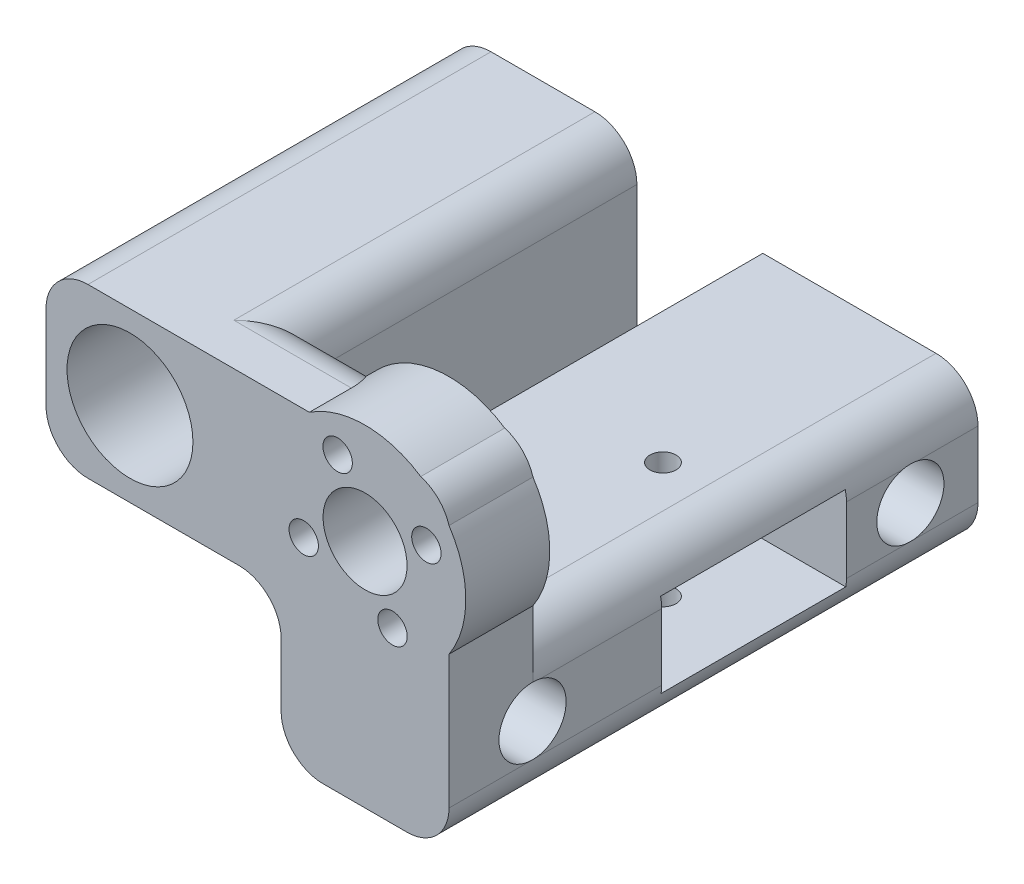
SolidWorks part; units mm, degrees
ref_plane "前视基准面" through (0, 0, 0) normal (0, 0, 1) x (1, 0, 0)
ref_plane "上视基准面" through (0, 0, 0) normal (0, 1, 0) x (1, 0, 0)
ref_plane "右视基准面" through (0, 0, 0) normal (1, 0, 0) x (0, 0, -1)
sketch "草图1" plane through (0, 0, 0) normal (0, 1, 0) x (1, 0, 0)
  line L1 (-10.5078, 7.8964) -> (37.4922, 7.8964)
  line L2 (-10.5078, 7.8964) -> (-10.5078, -40.1036)
  line L3 (-10.5078, -40.1036) -> (37.4922, -40.1036)
  line L4 (37.4922, 7.8964) -> (37.4922, -40.1036)
  line L5 (-10.5078, 7.8964) -> (37.4922, -40.1036) construction
  line L6 (-10.5078, -40.1036) -> (37.4922, 7.8964) construction
  point P4 (13.4922, -16.1036)
  dimension "D1" = 48
  dimension "D2" = 48
extrude "凸台-拉伸1" add sketch "草图1" along normal blind 40
sketch "草图2" plane through (0, 0, 40.1036) normal (0, 0, 1) x (1, 0, 0)
  line L0 (-10.5078, 40) -> (37.4922, 40) construction
  line L1 (-10.5078, 40) -> (-10.5078, 0) construction
  circle A0 centre (-0.5078, 30) radius 7.5
  circle A1 centre (27.4922, 30) radius 5
  circle A2 centre (24.2267, 37.3032) radius 1.75
  circle A3 centre (34.7954, 33.2656) radius 1.75
  circle A4 centre (20.1891, 26.7344) radius 1.75
  circle A5 centre (30.7578, 22.6968) radius 1.75
  dimension "D1" = 15
  dimension "D2" = 10
  dimension "D4" = 10
  dimension "D5" = 10
  dimension "D3" = 28
extrude "切除-拉伸1" cut sketch "草图2" against normal through all
sketch "草图3" plane through (0, 0, 40.1036) normal (0, 0, 1) x (1, 0, 0)
  circle A0 centre (27.4922, 30) radius 12
  circle A1 centre (27.4922, 30) radius 5.5
  circle A2 centre (24.2267, 37.3032) radius 1.75
  circle A3 centre (20.1891, 26.7344) radius 1.75
  circle A4 centre (30.7578, 22.6968) radius 1.75
  circle A5 centre (34.7954, 33.2656) radius 1.75
  dimension "D1" = 24
  dimension "D2" = 11
extrude "凸台-拉伸3" add sketch "草图3" against normal blind 10
sketch "草图4" plane through (0, 0, -7.8964) normal (0, 0, -1) x (-1, 0, 0)
  line L1 (-37.4922, 40) -> (-11.8688, 40)
  line L2 (-37.4922, 40) -> (-37.4922, 20.3994)
  line L3 (-37.4922, 20.3994) -> (-11.8688, 20.3994)
  line L4 (-11.8688, 40) -> (-11.8688, 20.3994)
  line L5 (-37.4922, 40) -> (-11.8688, 20.3994) construction
  line L6 (-37.4922, 20.3994) -> (-11.8688, 40) construction
  point P4 (-24.6805, 30.1997)
extrude "切除-拉伸2" cut sketch "草图4" against normal blind 38
fillet "圆角1" radius 5 1 edges at (37.4922, 40, 35.1036)
sketch "草图5" plane through (37.4922, 0, 0) normal (1, 0, 0) x (0, 0, -1)
  line L1 (-14.7696, 16.6006) -> (7.2304, 16.6006)
  line L2 (-14.7696, 16.6006) -> (-14.7696, 6.6006)
  line L3 (-14.7696, 6.6006) -> (7.2304, 6.6006)
  line L4 (7.2304, 16.6006) -> (7.2304, 6.6006)
  line L5 (-14.7696, 16.6006) -> (7.2304, 6.6006) construction
  line L18 (-14.7696, 6.6006) -> (7.2304, 16.6006) construction
  point P10 (0.3003, 11.5442)
  dimension "D1" = 10
  dimension "D2" = 22
extrude "切除-拉伸3" cut sketch "草图5" against normal through all
sketch "草图6" plane through (0, 0, 40.1036) normal (0, 0, 1) x (1, 0, 0)
  line L0 (37.4922, 0) -> (37.4922, 2.5)
  line L1 (37.4922, 23.3668) -> (37.4922, 0) construction
  line L2 (19.1148, 2.5) -> (47.1491, 2.5) construction
  line L3 (37.4922, 2.5) -> (17.4922, 2.5)
  line L4 (17.4922, 2.5) -> (17.4922, 20)
  line L5 (17.4922, 20) -> (-10.5078, 20)
  line L6 (-10.5078, 40) -> (-10.5078, 0) construction
  line L7 (-10.5078, 20) -> (-10.5078, 0)
  line L8 (-10.5078, 0) -> (37.4922, 0)
  dimension "D1" = 20
  dimension "D2" = 20
extrude "切除-拉伸4" cut sketch "草图6" against normal through all
fillet "圆角2" radius 5 7 edges at (16.3639, 40, 30.1036) (11.8688, 40, 11.1036) (37.4922, 2.5, 16.1036) (-10.5078, 40, 16.1036) (-10.5078, 20, 16.1036) (17.4922, 2.5, 16.1036) (17.4922, 20, 16.1036)
sketch "草图7" plane through (17.4922, 0, 0) normal (-1, 0, 0) x (0, 0, 1)
  line L0 (-7.8964, 20) -> (-7.8964, 2.5)
  line L1 (-7.8964, 2.5) -> (1.8729, 2.5)
  line L2 (40.1036, 2.5) -> (-7.8964, 2.5) construction
  line L3 (1.8729, 2.5) -> (1.8729, 20)
  line L4 (40.1036, 20) -> (-7.8964, 20) construction
  line L5 (1.8729, 20) -> (-7.8964, 20)
extrude "凸台-拉伸4" add sketch "草图7" along normal blind 23
fillet "圆角3" radius 5 3 edges at (17.4922, 2.5, -3.0117) (-5.5078, 20, -3.0117) (-5.5078, 2.5, -3.0117)
fillet "圆角4" radius 5 1 edges at (37.4922, 20.3994, 11.1036)
sketch "草图8" plane through (0, 20.3994, 0) normal (0, 1, 0) x (1, 0, 0)
  line L0 (37.4107, -3.7696) -> (17.5738, -3.7696) construction
  line L5 (37.4107, -14.7696) -> (37.4107, 7.2304) construction
  line L6 (17.5738, 7.2304) -> (17.5738, -14.7696) construction
  circle A0 centre (27.4922, -4.6224) radius 1.55
  dimension "D1" = 3.1
extrude "切除-拉伸5" cut sketch "草图8" against normal through all
sketch "草图10" plane through (0, 2.5, 0) normal (0, -1, 0) x (1, 0, 0)
  circle A1 centre (27.4922, 4.6224) radius 1.55
  circle A2 centre (27.4922, 4.6224) radius 4
  dimension "D1" = 8
extrude "凸台-拉伸6" add sketch "草图10" along normal blind 3
sketch "草图11" plane through (0, 0, 1.8729) normal (0, 0, 1) x (1, 0, 0)
  line L0 (12.4922, 2.5) -> (22.4922, 2.5)
  line L1 (22.4922, 2.5) -> (17.4922, 7.5)
  line L2 (17.4922, 7.5) -> (12.4922, 2.5)
  arc A0 (17.4922, 7.5) -> (22.4922, 2.5) centre (22.4922, 7.5) ccw construction
  arc A1 (12.4922, 2.5) -> (17.4922, 7.5) centre (12.4922, 7.5) ccw construction
extrude "凸台-拉伸7" add sketch "草图11" against normal up to surface (9.7692 mm away) up to face at (10.4725, 17.6278, -7.8964)
sketch "草图14" plane through (37.4922, 0, 0) normal (1, 0, 0) x (0, 0, -1)
  circle A0 centre (-30.1576, 11.5) radius 4
  dimension "D1" = 8
extrude "切除-拉伸7" cut sketch "草图14" against normal through all
sketch "草图17" plane through (0, 0, -7.8964) normal (0, 0, -1) x (-1, 0, 0)
  line L0 (-11.8688, 20.3994) -> (-11.8688, 2.5)
  line L7 (-32.4922, 2.5) -> (0.5078, 2.5)
  line L8 (5.5078, 7.5) -> (5.5078, 16.3397)
  line L9 (10.5078, 25) -> (10.5078, 35)
  line L10 (5.5078, 40) -> (-6.8688, 40)
  line L11 (-11.8688, 35) -> (-11.8688, 20.3994)
  line L12 (-11.8688, 20.3994) -> (-32.4922, 20.3994)
  line L13 (-37.4922, 15.3994) -> (-37.4922, 7.5)
  line L14 (-32.4922, 2.5) -> (-11.8688, 2.5)
  line L19 (-11.8688, 20.3994) -> (-32.4922, 20.3994)
  line L20 (-37.4922, 15.3994) -> (-37.4922, 7.5)
  arc A7 (0.5078, 2.5) -> (5.5078, 7.5) centre (0.5078, 7.5) ccw
  arc A8 (8.0078, 20.6699) -> (5.5078, 16.3397) centre (10.5078, 16.3397) ccw
  arc A9 (8.0078, 20.6699) -> (10.5078, 25) centre (5.5078, 25) ccw
  arc A10 (10.5078, 35) -> (5.5078, 40) centre (5.5078, 35) ccw
  arc A11 (-6.8688, 40) -> (-11.8688, 35) centre (-6.8688, 35) ccw
  arc A12 (-32.4922, 20.3994) -> (-37.4922, 15.3994) centre (-32.4922, 15.3994) ccw
  arc A13 (-37.4922, 7.5) -> (-32.4922, 2.5) centre (-32.4922, 7.5) ccw
  arc A19 (-32.4922, 20.3994) -> (-37.4922, 15.3994) centre (-32.4922, 15.3994) ccw
  arc A20 (-37.4922, 7.5) -> (-32.4922, 2.5) centre (-32.4922, 7.5) ccw
  dimension "D1" = 0
extrude "凸台-拉伸8" add sketch "草图17" along normal blind 15
sketch "草图18" plane through (11.8688, 0, 0) normal (-1, 0, 0) x (0, 0, 1)
  circle A0 centre (-14.8424, 11.5) radius 4
extrude "切除-拉伸10" cut sketch "草图18" against normal through all
sketch "草图16" plane through (37.4922, 0, 0) normal (1, 0, 0) x (0, 0, -1)
  circle A0 centre (14.8424, 11.5) radius 4
extrude "切除-拉伸8" cut sketch "草图16" against normal through all rebuild error yes
